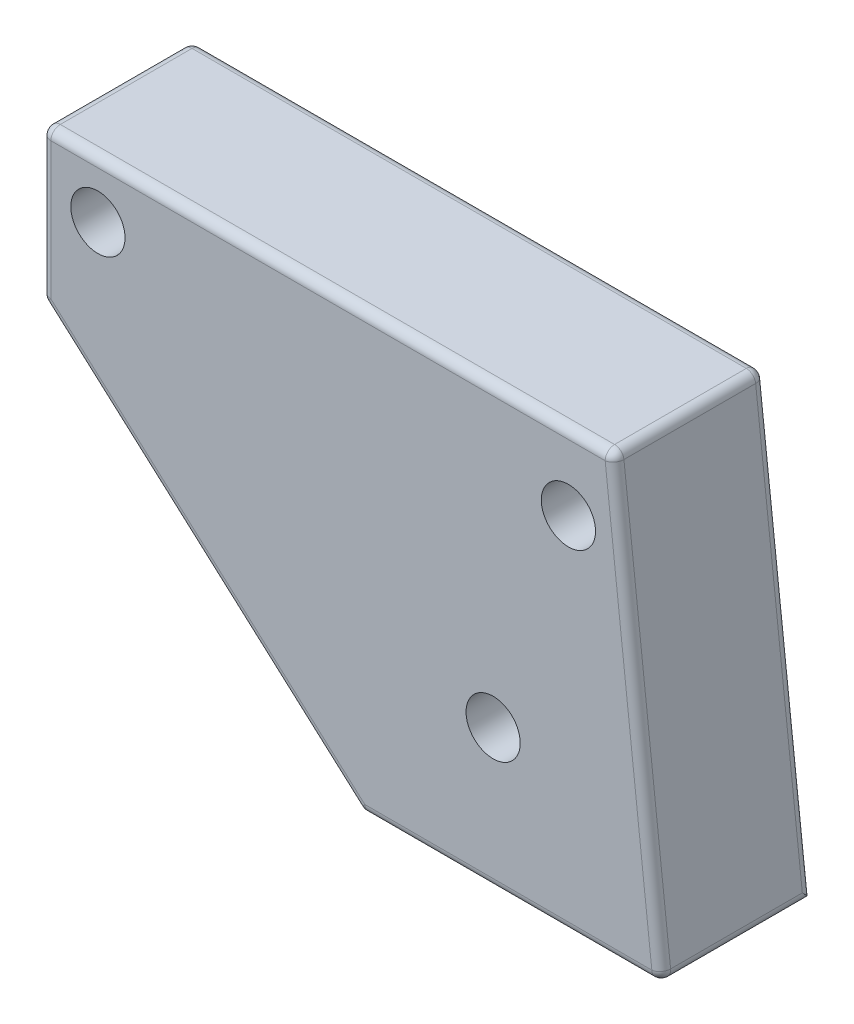
SolidWorks part; units mm, degrees
ref_plane "Front Plane" through (0, 0, 0) normal (0, 0, 1) x (1, 0, 0)
ref_plane "Top Plane" through (0, 0, 0) normal (0, 1, 0) x (1, 0, 0)
ref_plane "Right Plane" through (0, 0, 0) normal (1, 0, 0) x (0, 0, -1)
sketch "Sketch1" plane through (0, 0, 0) normal (0, 0, 1) x (1, 0, 0)
  line L1 (-25.4, 0) -> (0, 0)
  line L2 (0, 0) -> (-4.1148, 36.83)
  line L3 (-4.1148, 36.83) -> (-52.3748, 36.83)
  line L4 (328.6252, 36.83) -> (-52.3748, 36.83) construction
  line L5 (-52.3748, 36.83) -> (-52.3748, 24.13)
  line L6 (-52.3748, 36.83) -> (-52.3748, -7.62) construction
  line L7 (-52.3748, 24.13) -> (-25.4, 0)
  circle A0 centre (-47.6123, 32.0675) radius 2.286
  circle A1 centre (-7.9248, 30.48) radius 2.286
  circle A2 centre (-14.2748, 11.8269) radius 2.286
  point P15 (-52.3748, 36.83)
  point P17 (0, 36.83)
  point P18 (-14.2748, 11.8269)
  point P19 (-25.4, 0)
  point P26 (0, 36.83)
  point P27 (0, 36.83)
  point P28 (-3.95, 36.83)
  dimension "D3" = 4.572
  dimension "D1" = 25.4
  dimension "D2" = 12.7
  dimension "D4" = 48.26
extrude "Boss-Extrude1" add sketch "Sketch1" along normal blind 12.7
sketch "Sketch3" plane through (0, 0, 0) normal (0, -1, 0) x (1, 0, 0)
  line L1 (0, 12.7) -> (0, 0) construction
  line L3 (-25.4, 0) -> (0, 0) construction
  circle A0 centre (-19.05, 6.35) radius 1.905
  circle A1 centre (-6.35, 6.35) radius 1.905
  point P4 (0, 0)
  point P9 (-19.05, 6.35)
  point P10 (-19.05, 6.35)
  point P11 (-19.05, 6.35)
  dimension "D1" = 3.81
  dimension "D2" = 6.35
  dimension "D3" = 12.7
  dimension "D4" = 6.35
extrude "Cut-Extrude1" cut sketch "Sketch3" against normal blind 25.4
fillet "Fillet1" radius 0.7937 14 edges at (-52.3748, 30.48, 12.7) (-52.3748, 30.48, 0) (-52.3748, 24.13, 6.35) (-38.8874, 12.065, 12.7) (-25.4, 0, 6.35) (-38.8874, 12.065, 0) (0, 0, 6.35) (-2.0574, 18.415, 12.7) (-2.0574, 18.415, 0) (-4.1148, 36.83, 6.35) (-28.2448, 36.83, 12.7) (-52.3748, 36.83, 6.35) (-28.2448, 36.83, 0) (-12.7, 0, 12.7)
